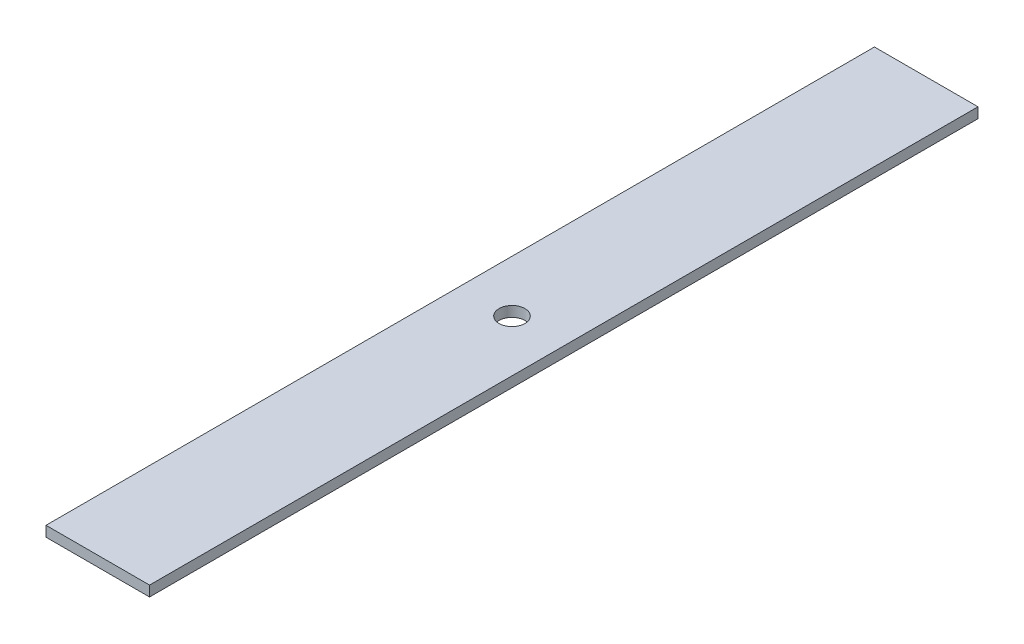
SolidWorks part; units mm, degrees
ref_plane "Front Plane" through (0, 0, 0) normal (0, 0, 1) x (1, 0, 0)
ref_plane "Top Plane" through (0, 0, 0) normal (0, 1, 0) x (1, 0, 0)
ref_plane "Right Plane" through (0, 0, 0) normal (1, 0, 0) x (0, 0, -1)
sketch "sketch" plane through (0, 0, 0) normal (0, 1, 0) x (1, 0, 0)
  line L1 (0, 0) -> (25.4, 0)
  line L2 (0, 0) -> (0, 203.2)
  line L3 (0, 203.2) -> (25.4, 203.2)
  line L4 (25.4, 0) -> (25.4, 203.2)
  circle A0 centre (12.7, 101.6) radius 3.175
  dimension "D3" = 6.35
  dimension "D1" = 25.4
  dimension "D2" = 203.2
  dimension "D4" = 12.7
  dimension "D5" = 101.6
extrude "Boss-Extrude2" add sketch "sketch" along normal blind 2.54
